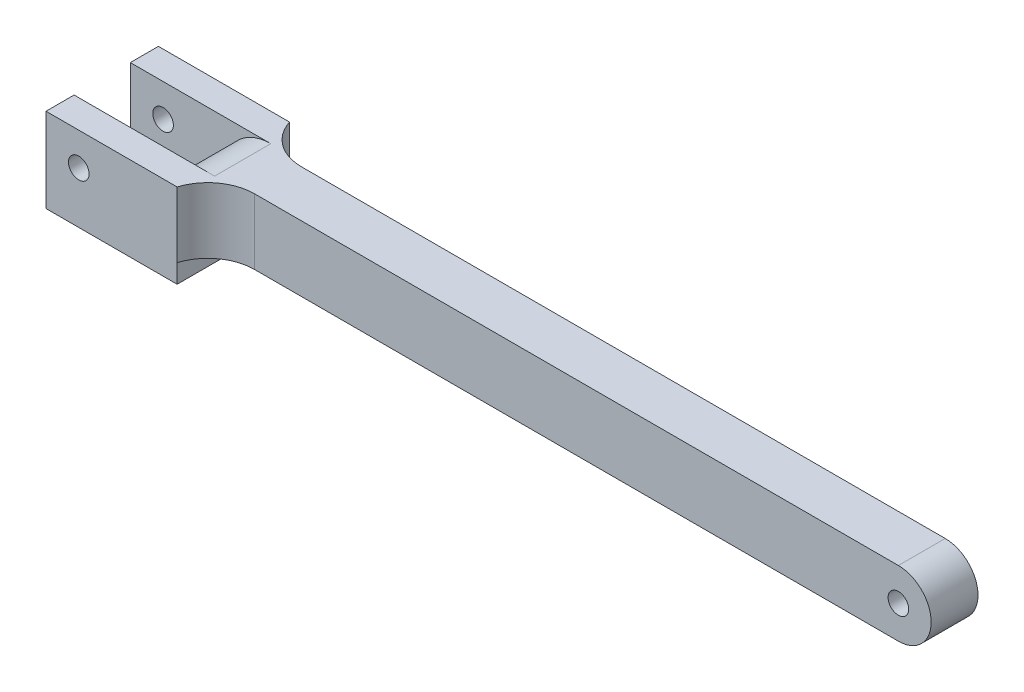
SolidWorks part; units mm, degrees
ref_plane "Front Plane" through (0, 0, 0) normal (0, 0, 1) x (1, 0, 0)
ref_plane "Top Plane" through (0, 0, 0) normal (0, 1, 0) x (1, 0, 0)
ref_plane "Right Plane" through (0, 0, 0) normal (1, 0, 0) x (0, 0, -1)
sketch "Sketch1" plane through (0, 0, 0) normal (0, 0, 1) x (1, 0, 0)
  line L0 (0, 0) -> (83.5, 0) construction
  line L1 (0, 3.5) -> (83.5, 3.5)
  line L2 (0, -3.5) -> (83.5, -3.5)
  circle A0 centre (0, 0) radius 1.1
  circle A1 centre (0, 0) radius 3.5
  circle A2 centre (83.5, 0) radius 1.1
  circle A3 centre (83.5, 0) radius 3.5
  dimension "D1" = 83.5
extrude "Boss-Extrude1" add sketch "Sketch1" along normal blind 5 contours A0 A1 | A1 L0 A3 L1 | A3 A2 | L0 A1 L2 A3 region at (2.4049, -2.4049, 0) region at (41.75, 1.7686, 0) region at (41.75, -1.7686, 0) region at (81.0951, 2.4049, 0)
sketch "Sketch4" plane through (0, 3.5, 0) normal (0, 1, 0) x (1, 0, 0)
  line L1 (-4, 3.5) -> (10, 3.5)
  line L2 (-4, 3.5) -> (-4, -8.5)
  line L3 (-4, -8.5) -> (10, -8.5)
  line L4 (10, 3.5) -> (10, -8.5)
  line L5 (0, -5) -> (83.5, -5) construction
  line L6 (0, -5) -> (0, 0) construction
  dimension "D1" = 14
  dimension "D2" = 12
  dimension "D3" = 3.5
  dimension "D4" = 10
extrude "Boss-Extrude3" add sketch "Sketch4" against normal blind 9
sketch "Sketch5" plane through (0, -5.5, 0) normal (0, -1, 0) x (1, 0, 0)
  line L0 (-4, -3.5) -> (-4, 8.5) construction
  line L1 (-4, 5.5) -> (6, 5.5)
  line L2 (-4, 5.5) -> (-4, -0.5)
  line L3 (-4, -0.5) -> (6, -0.5)
  line L4 (6, 5.5) -> (6, -0.5)
  line L5 (-4, 8.5) -> (10, 8.5) construction
  dimension "D1" = 6
  dimension "D2" = 3
  dimension "D3" = 10
extrude "Cut-Extrude2" cut sketch "Sketch5" against normal blind 9
sketch "Sketch7" plane through (0, 0, 0) normal (0, 0, -1) x (-1, 0, 0)
  line L0 (4, -5.5) -> (4, 3.5) construction
  circle A0 centre (0.5, 0) radius 1.1
  dimension "D1" = 3.5
extrude "Cut-Extrude3" cut sketch "Sketch7" against normal blind 15 from offset 5
fillet "Fillet1" radius 5 2 edges at (10, 0, 5) (10, 0, 0)
fillet "Fillet2" radius 5 1 edges at (6, 3.5, 2.5)
